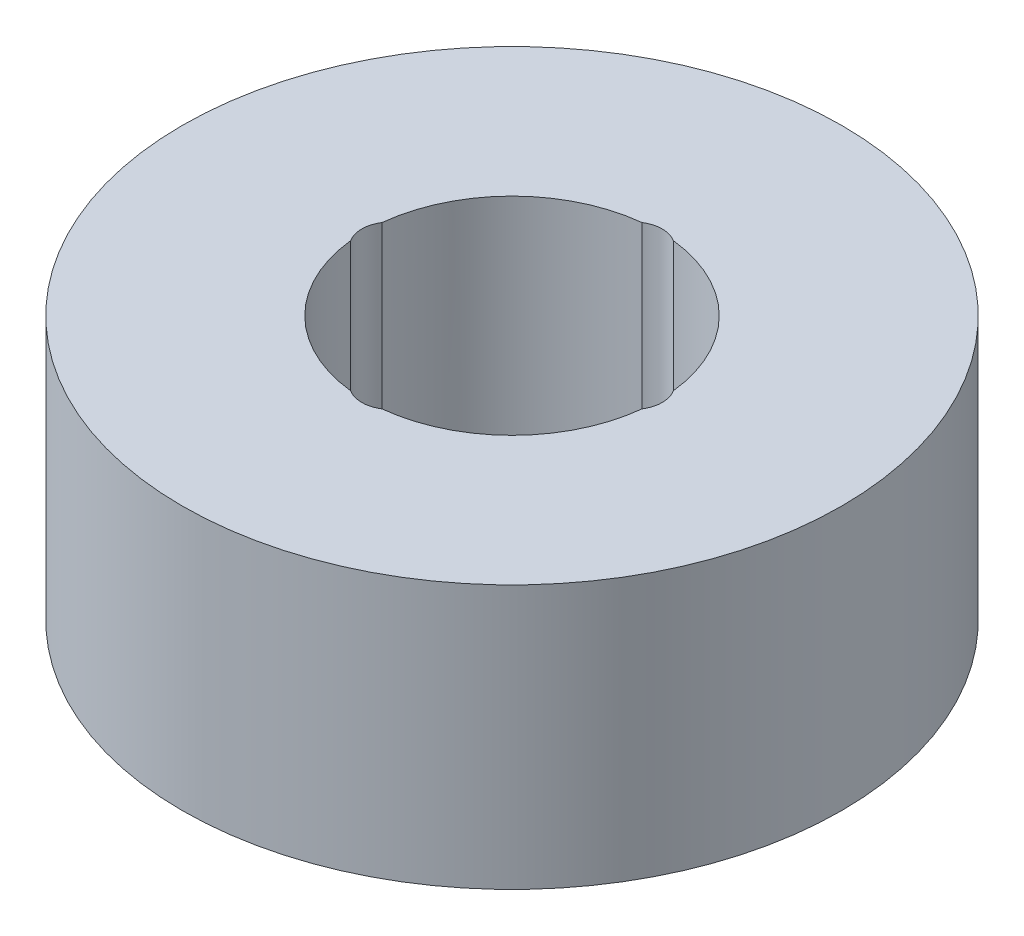
SolidWorks part; units mm, degrees
ref_plane "Front Plane" through (0, 0, 0) normal (0, 0, 1) x (1, 0, 0)
ref_plane "Top Plane" through (0, 0, 0) normal (0, 1, 0) x (1, 0, 0)
ref_plane "Right Plane" through (0, 0, 0) normal (1, 0, 0) x (0, 0, -1)
sketch "Sketch1" plane through (0, 0, 0) normal (0, 1, 0) x (1, 0, 0)
  circle A0 centre (0, 0) radius 22.5
  dimension "FLANGE_OD" = 45
extrude "Boss-Extrude1" add sketch "Sketch1" along normal blind 18
sketch "Sketch2" plane through (0, 0, 0) normal (0, 1, 0) x (1, 0, 0)
  circle A0 centre (0, 0) radius 10
  dimension "BORE_D" = 20
extrude "Cut-Extrude1" cut sketch "Sketch2" along normal through all
sketch "Sketch3" plane through (0, 18, 0) normal (0, 1, 0) x (1, 0, 0)
  circle A0 centre (0, 0) radius 8.2559 construction
  circle A1 centre (-8.2559, 0) radius 1.9984
  dimension "BOLT_D" = 3.9967
  dimension "BOLT_PCD" = 16.5118
extrude "Cut-Extrude2" cut sketch "Sketch3" against normal blind 14.2822
pattern_circular "CirPattern1" count 4 over 360 about axis through (0, 0, 0) along (0, 1, 0) of "Cut-Extrude2"
